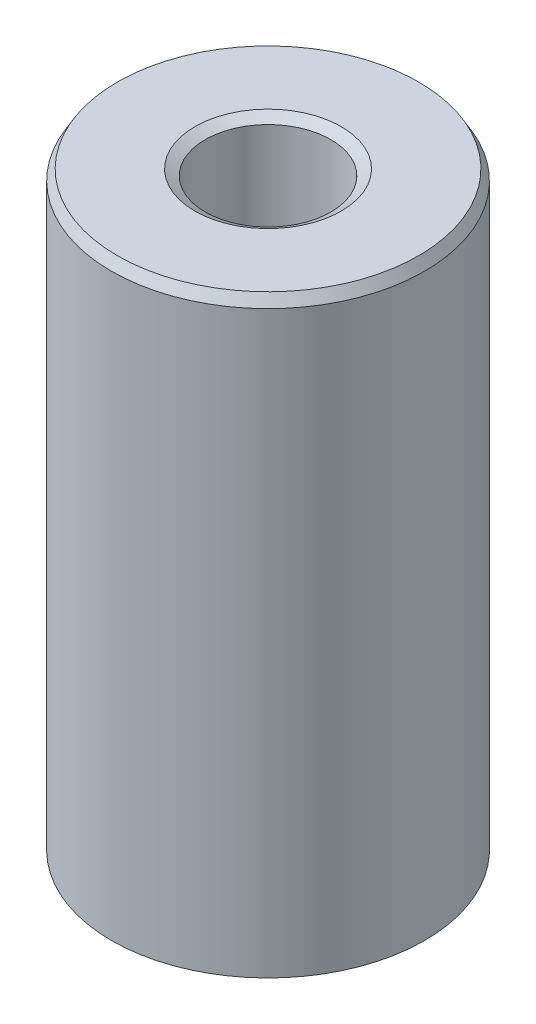
SolidWorks part; units mm, degrees
ref_plane "Front Plane" through (0, 0, 0) normal (0, 0, 1) x (1, 0, 0)
ref_plane "Top Plane" through (0, 0, 0) normal (0, 1, 0) x (1, 0, 0)
ref_plane "Right Plane" through (0, 0, 0) normal (1, 0, 0) x (0, 0, -1)
sketch "Sketch1" plane through (0, 0, 0) normal (0, 1, 0) x (1, 0, 0)
  circle A0 centre (0, 0) radius 7.5
  dimension "SLEEVE_OD" = 15
extrude "Boss-Extrude1" add sketch "Sketch1" along normal blind 28.5537
sketch "Sketch2" plane through (0, 0, 0) normal (0, 1, 0) x (1, 0, 0)
  circle A0 centre (0, 0) radius 3.0081
  dimension "BORE_D" = 6.0162
extrude "Cut-Extrude1" cut sketch "Sketch2" along normal through all
chamfer "Chamfer1" distance 0.4981 angle 30 4 edges at (0, 28.5537, 3.0081) (0, 0, 3.0081) (0, 0, 7.5) (0, 28.5537, 7.5) first distance on face at (0, 28.5537, 3.0081) first distance on face at (0, 0, 3.0081) first distance on face at (0, 28.5537, 7.5)
